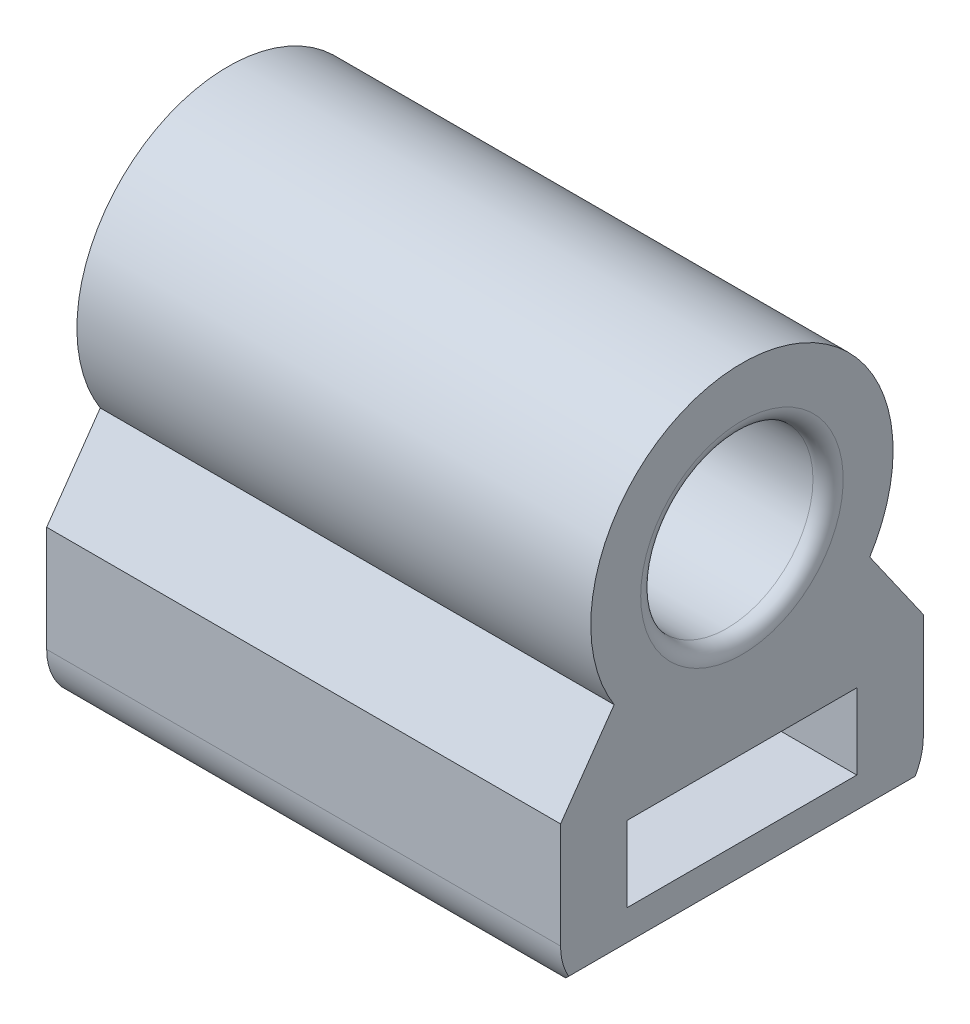
SolidWorks part; units mm, degrees
material "聚脂树脂"
ref_plane "前视基准面" through (0, 0, 0) normal (0, 0, 1) x (1, 0, 0)
ref_plane "上视基准面" through (0, 0, 0) normal (0, 1, 0) x (1, 0, 0)
ref_plane "右视基准面" through (0, 0, 0) normal (1, 0, 0) x (0, 0, -1)
other "Configuration Table"
sketch "草图1" plane through (0, 0, 0) normal (0, 1, 0) x (1, 0, 0)
  line L0 (0, 0) -> (-10.1512, 0) construction
  line L1 (0, 0) -> (9.7077, 0) construction
  line L2 (-6, -6) -> (6, -6)
  line L3 (-6, -6) -> (-6, 6)
  line L4 (-6, 6) -> (6, 6)
  line L5 (6, -6) -> (6, 6)
  line L6 (-6, -6) -> (6, 6) construction
  line L7 (-6, 6) -> (6, -6) construction
  line L8 (-6, 6) -> (-11, 6)
  line L9 (-11, 6) -> (-11, -6)
  line L10 (-11, -6) -> (-6, -6)
  line L11 (6, 6) -> (16, 6)
  line L12 (16, 6) -> (16, -6)
  line L13 (16, -6) -> (6, -6)
  circle A0 centre (11, 0) radius 3.5
  circle A1 centre (-2.5, 0) radius 1
  circle A2 centre (2.5, 0) radius 1
  point P1 (0, 0)
  dimension "D1" = 2
  dimension "D2" = 2
  dimension "D3" = 7
  dimension "D4" = 8.5
  dimension "D5" = 13.5
  dimension "D6" = 11
  dimension "D7" = 12
  dimension "D8" = 12
  dimension "D9" = 5
  dimension "D10" = 10
extrude "凸台-拉伸1" add sketch "草图1" along normal blind 2 contours L2 L5 L4 L3 A2 A1 | L9 L10 L3 L8 | A0
sketch "草图2" plane through (0, 2, 0) normal (0, 1, 0) x (1, 0, 0)
  line L0 (-11, 6) -> (6, 6) construction
  line L1 (-2.7028, 2.3111) -> (10.6941, 3.4866) construction
  line L2 (-2.7028, -2.3111) -> (10.6941, -3.4866) construction
  line L3 (-11, 6) -> (6, 6)
  line L4 (6, 6) -> (6, 3.8)
  line L5 (6, -6) -> (6, 6) construction
  line L6 (6, 3.8) -> (-11, 3.8)
  line L8 (-11, 3.8) -> (-11, 6)
  line L9 (-2.5, 0) -> (3.5, 0) construction
  line L10 (6, -3.8) -> (-11, -3.8)
  line L11 (6, -6) -> (6, -3.8)
  line L12 (-11, -6) -> (6, -6)
  line L13 (-11, -3.8) -> (-11, -6)
  line L14 (-11, 6) -> (-11, -6) construction
  line L15 (-11, 6) -> (6, 6) construction
  circle A0 centre (-2.5, 0) radius 2.32 construction
  circle A1 centre (11, 0) radius 3.5 construction
  circle A2 centre (2.5, 0) radius 1 construction
  dimension "D1" = 4.64
  dimension "D2" = 7
  dimension "D3" = 13.5
  dimension "D4" = 6
  dimension "D5" = 2.2
extrude "凸台-拉伸2" add sketch "草图2" along normal blind 2.5
sketch "草图4" plane through (6, 0, 0) normal (1, 0, 0) x (0, 0, -1)
  line L0 (-6, 4.5) -> (6, 4.5)
  line L1 (6, 4.5) -> (6, 5.5)
  line L2 (-6, 4.5) -> (-6, 5.5)
  line L3 (0, 0) -> (0, 14.0545) construction
  line L4 (-6, 5.5) -> (-4.2279, 8.0308)
  line L5 (6, 5.5) -> (4.2279, 8.0308)
  circle A0 centre (0, 10.7) radius 5
  circle A1 centre (0, 10.7) radius 2.85
  dimension "D2" = 145
  dimension "D3" = 1
  dimension "D1" = 10
  dimension "D4" = 5.7
  dimension "D5" = 6.2
extrude "凸台-拉伸3" add sketch "草图4" against normal up to surface (17 mm away)
fillet "圆角1" radius 0.5 2 edges at (6, 10.7, -2.85) (-11, 10.7, -2.85)
chamfer "倒角1" distance 1 angle 45 1 edges at (6, 0, 0)
fillet "圆角4" radius 2 2 edges at (-3, 0, -6) (-3, 0, 6)
